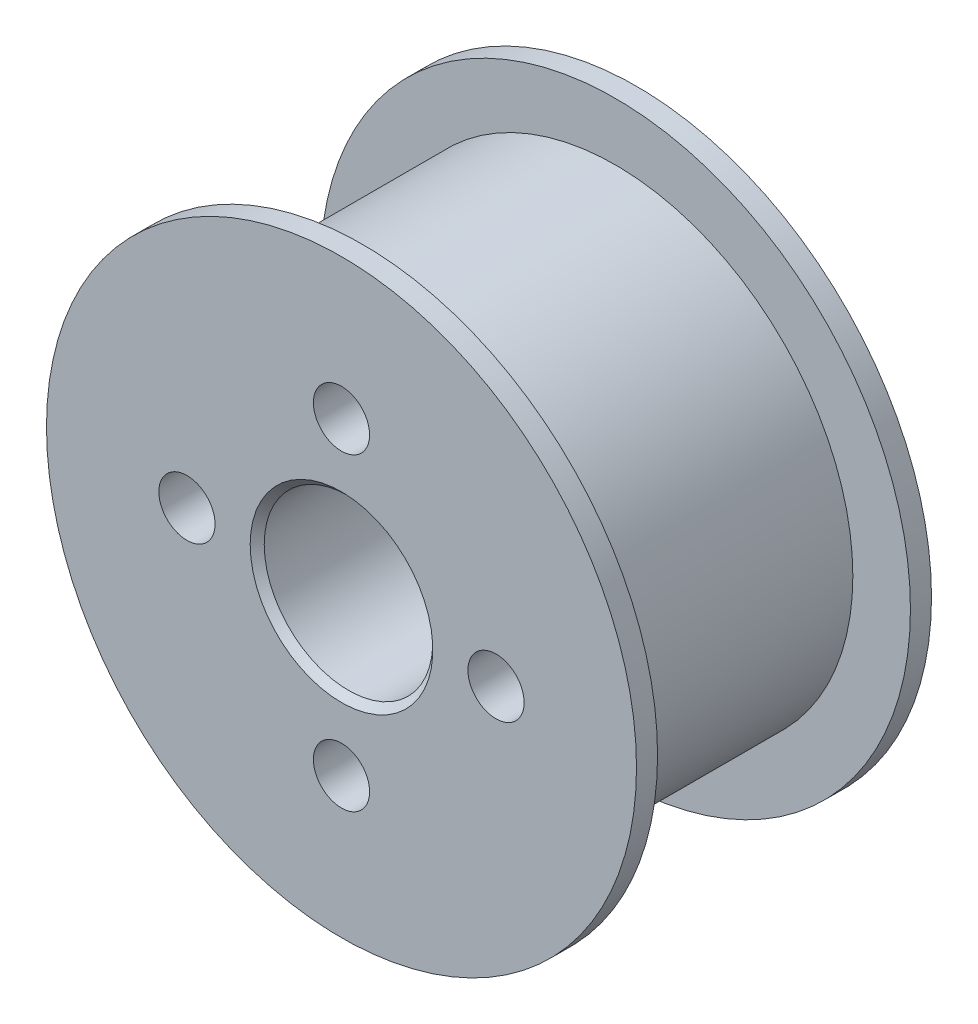
SolidWorks part; units mm, degrees
material "1060 Alloy"
ref_plane "Front Plane" through (0, 0, 0) normal (0, 0, 1) x (1, 0, 0)
ref_plane "Top Plane" through (0, 0, 0) normal (0, 1, 0) x (1, 0, 0)
ref_plane "Right Plane" through (0, 0, 0) normal (1, 0, 0) x (0, 0, -1)
sketch "Sketch1" plane through (0, 0, 0) normal (1, 0, 0) x (0, 0, -1)
  line L0 (0, 0) -> (26, 0)
  line L1 (21, 13) -> (21, 21)
  line L2 (21, 21) -> (19.5, 21)
  line L3 (0, 21) -> (0, 0)
  line L4 (1.5, 21) -> (1.5, 16.9)
  line L5 (1.5, 16.9) -> (19.5, 16.9)
  line L6 (19.5, 16.9) -> (19.5, 21)
  line L7 (1.5, 21) -> (0, 21)
  line L8 (21, 13) -> (26, 13)
  line L9 (26, 13) -> (26, 0)
  dimension "D1" = 18
  dimension "D2" = 16.9
  dimension "D3" = 21
  dimension "D4" = 21
  dimension "D5" = 13
  dimension "D6" = 5
ref_axis "Axis1" through (0, 0, 0) along (0, 0, -1)
revolve "Revolve1" add sketch "Sketch1" angle 360 about L0
sketch "Sketch2" plane through (0, 0, -26) normal (0, 0, -1) x (-1, 0, 0)
  circle A0 centre (0, 0) radius 6
  dimension "D1" = 12
extrude "Cut-Extrude1" cut sketch "Sketch2" against normal through all
hole_wizard "CBORE for M4 Hex Socket Head Cap Screw1" positions "Sketch3" profile "Sketch4" counterbore size "M4" standard "ISO" end condition through all
sketch "Sketch3" plane through (0, 0, -26) normal (0, 0, -1) x (-1, 0, 0)
  circle A0 centre (0, 0) radius 11 construction
  point P0 (0, 11)
  point P10 (11, 0)
  point P12 (0, -11)
  point P14 (-11, 0)
  dimension "D1" = 22
sketch "Sketch4" plane through (0, 11, -26) normal (1, 0, 0) x (0, 1, 0)
  line L0 (0, 0) -> (0, 26)
  line L1 (0, 26) -> (2, 26)
  line L3 (2, 26) -> (2, 5)
  line L4 (2, 5) -> (4, 5)
  line L5 (4, 5) -> (4, 0)
  line L7 (4, 0) -> (0, 0)
  line L11 (0, -6.35) -> (0, 107.95) construction
  dimension "Thru Hole Dia." = 4
  dimension "Thru Hole Depth" = 26
  dimension "C'Bore Dia." = 8
  dimension "C'Bore Depth" = 5
chamfer "Chamfer1" distance 0.5 angle 45 1 edges at (0, 6, 0)
